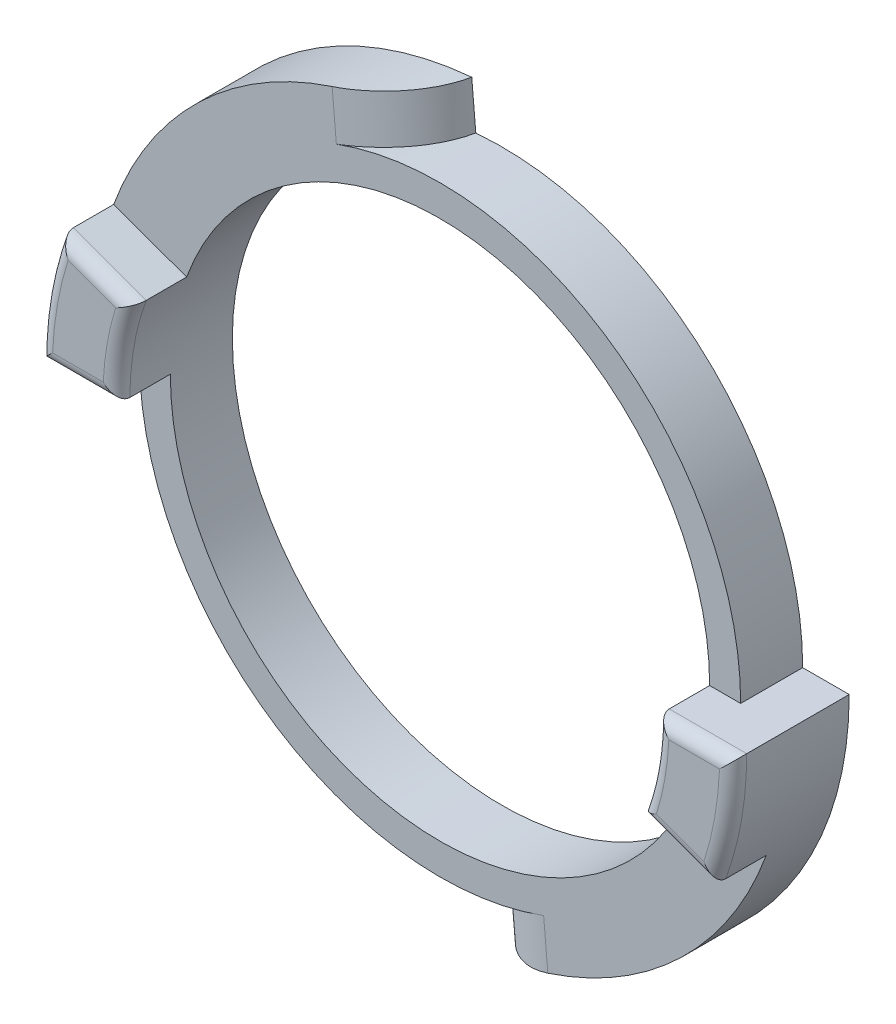
SolidWorks part; units mm, degrees
ref_plane "Front Plane" through (0, 0, 0) normal (0, 0, 1) x (1, 0, 0)
ref_plane "Top Plane" through (0, 0, 0) normal (0, 1, 0) x (1, 0, 0)
ref_plane "Right Plane" through (0, 0, 0) normal (1, 0, 0) x (0, 0, -1)
sketch "Sketch2" plane through (0, 0, 0) normal (0, 0, 1) x (1, 0, 0)
  line L0 (0, 0) -> (-1.1803, 13.4911)
  line L1 (0, 0) -> (1.5834, -18.0981)
  line L2 (0, 11.15) -> (0, 13) construction
  line L4 (0, 0) -> (-13, 0)
  line L5 (0, 0) -> (13, 0)
  circle A0 centre (0, 0) radius 12.875
  circle A2 centre (0, 0) radius 10
  circle A3 centre (0, 0) radius 11.15
  arc M8 (-11.15, 0) -> (10.1053, 4.7122) centre (0, 0) cw
  dimension "D2" = 25.75
  dimension "D1" = 5
extrude "Boss-Extrude1" add sketch "Sketch2" along normal blind 2.3 contours L0 A0 L4 M8 | A2 L0 L4 M8 | L5 A3 L0 A2 M8 | L1 A3 L5 A2 | L4 A3 L1 A2 | A3 L1 A0 L5 region at (-7.4843, 6.8581, 0) region at (-0.7576, 10.5491, 0) region at (7.4843, -6.8581, 0) region at (0.7576, -10.5491, 0) region at (-8.3497, 7.651, 0) region at (8.3497, -7.651, 0)
fillet "Fillet1" radius 3 2 edges at (-1.047, 11.9668, 2.3) (1.047, -11.9668, 2.3)
sketch "Sketch3" plane through (0, 0, 2.3) normal (0, 0, 1) x (1, 0, 0)
  line L0 (0, 0) -> (-14.1763, 5.1598)
  line L1 (0, 0) -> (15.4887, -5.6374)
  line L2 (-12.875, 0) -> (-11.15, 0) construction
  line L3 (0, 0) -> (-11.15, 0)
  line L4 (0, 0) -> (11.15, 0)
  line L7 (-3.844, 10.4664) -> (-3.999, 12.2382)
  line L8 (-12.875, 0) -> (-11.15, 0)
  line L9 (3.844, -10.4664) -> (3.999, -12.2382)
  line L10 (12.875, 0) -> (11.15, 0)
  line L11 (-3.844, 10.4664) -> (-3.999, 12.2382)
  line L12 (-12.875, 0) -> (-11.15, 0)
  line L13 (3.844, -10.4664) -> (3.999, -12.2382)
  line L14 (12.875, 0) -> (11.15, 0)
  arc A4 (11.15, 0) -> (-3.844, 10.4664) centre (0, 0) ccw
  arc A5 (-3.999, 12.2382) -> (-12.875, 0) centre (0, 0) ccw
  arc A6 (-11.15, 0) -> (3.844, -10.4664) centre (0, 0) ccw
  arc A7 (3.999, -12.2382) -> (12.875, 0) centre (0, 0) ccw
  arc A8 (11.15, 0) -> (-3.844, 10.4664) centre (0, 0) ccw
  arc A9 (-3.999, 12.2382) -> (-12.875, 0) centre (0, 0) ccw
  arc A10 (-11.15, 0) -> (3.844, -10.4664) centre (0, 0) ccw
  arc A11 (3.999, -12.2382) -> (12.875, 0) centre (0, 0) ccw
  arc M12 (-3.999, 12.2382) -> (-12.875, 0) centre (0, 0) ccw
  line M13 (-12.875, 0) -> (-11.15, 0)
  arc M16 (3.999, -12.2382) -> (12.875, 0) centre (0, 0) ccw
  line M17 (12.875, 0) -> (11.15, 0)
  circle M18 centre (0, 0) radius 10
  dimension "D1" = 20
  dimension "D2" = 0
extrude "Boss-Extrude2" add sketch "Sketch3" along normal blind 2 contours L3 L0 M18 M12 M13 | L4 L1 M18 M16 M17 region at (-11.2656, 1.9864, 2.3) region at (11.2656, -1.9864, 2.3)
fillet "Fillet2" radius 0.5 8 edges at (12.6794, -2.2357, 4.3) (10.7477, -3.9119, 4.3) (9.8481, -1.7365, 4.3) (11.4375, 0, 4.3) (-12.6794, 2.2357, 4.3) (-10.7477, 3.9119, 4.3) (-9.8481, 1.7365, 4.3) (-11.4375, 0, 4.3)
